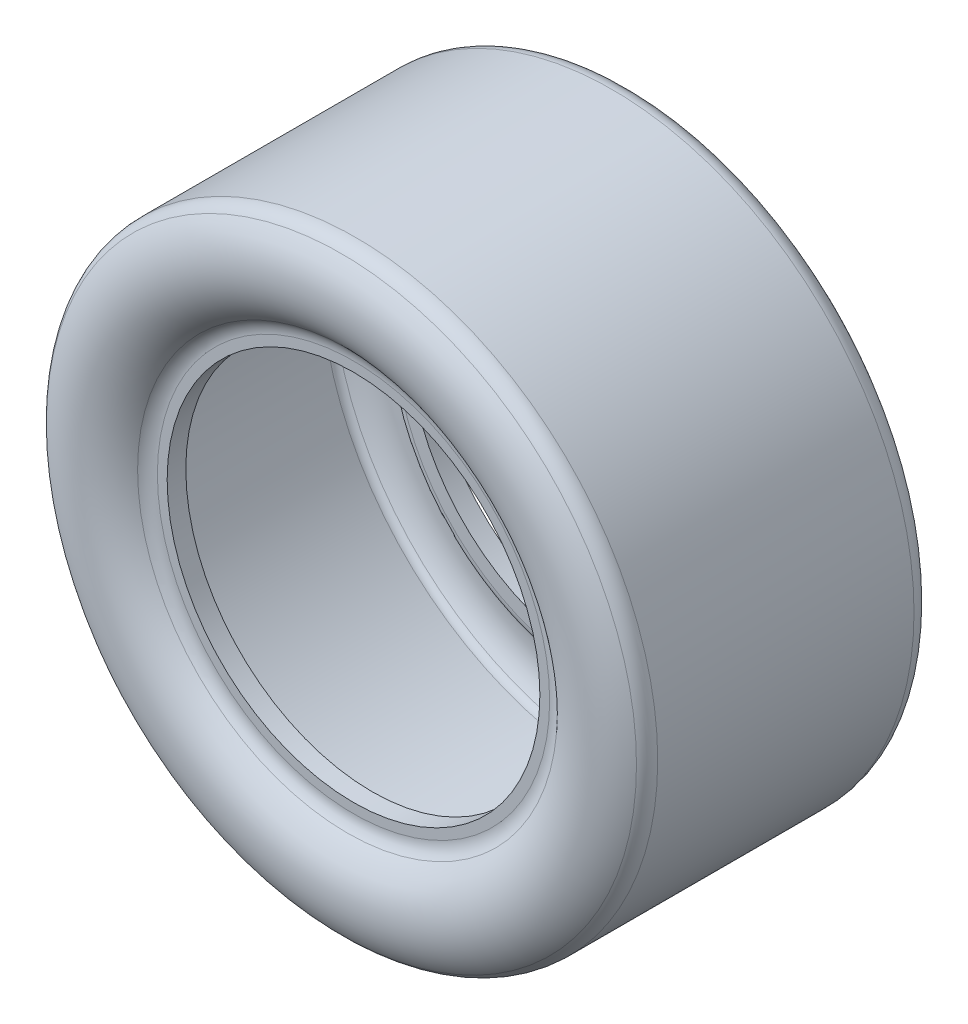
SolidWorks part; units mm, degrees
material "Tire Rubber"
ref_plane "X-Z Datum" through (0, 0, 0) normal (0, 0, 1) x (1, 0, 0)
ref_plane "X-Y Datum" through (0, 0, 0) normal (0, 1, 0) x (1, 0, 0)
ref_plane "Y-Z Plane" through (0, 0, 0) normal (1, 0, 0) x (0, 0, -1)
sketch "Sketch1" plane through (0, 0, 0) normal (1, 0, 0) x (0, 0, -1)
  line L0 (0, 0) -> (-132272.0706, 0) construction
  line L1 (-92.71, 205.74) -> (92.71, 205.74)
  line L2 (0, 0) -> (0, -132272.0706) construction
  line L4 (-88.9, 127) -> (-88.9, 139.7)
  line L5 (88.9, 127) -> (88.9, 139.7)
  line L6 (-88.9, 127) -> (-76.2, 127)
  line L8 (76.2, 127) -> (88.9, 127)
  line L9 (-76.2, 127) -> (-76.2, 136.7746)
  line L10 (76.2, 127) -> (76.2, 136.7746)
  line L11 (-86.5663, 197.8025) -> (86.5663, 197.8025)
  arc A2 (-92.71, 205.74) -> (-88.9, 139.7) centre (-64.4017, 174.2433) ccw
  arc A3 (92.71, 205.74) -> (88.9, 139.7) centre (64.4017, 174.2433) cw
  arc A4 (-91.5819, 195.3468) -> (-80.4384, 143.7974) centre (-64.4017, 174.2433) ccw
  arc A5 (-86.5663, 197.8025) -> (-91.5819, 195.3468) centre (-86.5663, 191.4525) ccw
  arc A6 (-76.2, 136.7746) -> (-80.4384, 143.7974) centre (-84.1375, 136.7746) ccw
  arc A7 (91.5819, 195.3468) -> (80.4384, 143.7974) centre (64.4017, 174.2433) cw
  arc A8 (86.5663, 197.8025) -> (91.5819, 195.3468) centre (86.5663, 191.4525) cw
  arc A9 (80.4384, 143.7974) -> (76.2, 136.7746) centre (84.1375, 136.7746) ccw
  point P7 (-106.68, 171.8041)
  dimension "D4" = 213.36
  dimension "D9" = 7.9375
  dimension "D10" = 6.35
  dimension "D11" = 7.9375
  dimension "D12" = 7.9375
  dimension "D1" = 185.42
  dimension "D2" = 411.48
  dimension "D3" = 12.7
  dimension "D5" = 177.8
  dimension "D6" = 254
  dimension "D7" = 12.7
  dimension "D8" = 7.9375
revolve "Revolve1" add sketch "Sketch1" angle 360 about L0
fillet "Fillet1" radius 12.7 4 edges at (-139.7, 0, -88.9) (-139.7, 0, 88.9) (-205.74, 0, -92.71) (-205.74, 0, 92.71)
ref_axis "Axis1" [suppressed] through (0, 0, 87.3303) along (0, 0, -1)
sketch "Sketch2" plane through (0, 0, 0) normal (0, 0, 1) x (1, 0, 0)
  circle A0 centre (0, 0) radius 205.74
  dimension "D1" = 411.48
extrude "Boss-Extrude1" [suppressed] add sketch "Sketch2" along normal mid plane 185.42
fillet "Fillet2" [suppressed] radius 25.4
sketch "Sketch3" plane through (0, 0, 0) normal (1, 0, 0) x (0, 0, -1)
  line L0 (0, 0) -> (0, 170833.7536) construction
  line L1 (0, 0) -> (-170833.7536, 0) construction
  line L2 (106.68, 205.74) -> (-106.68, 205.74)
  line L3 (-106.68, 205.74) -> (-106.68, 0)
  line L4 (106.68, 205.74) -> (106.68, 0)
  line L5 (106.68, 0) -> (-106.68, 0)
  point P7 (0, 205.74)
  dimension "D1" = 213.36
  dimension "D2" = 411.48
revolve "Revolve2" [suppressed] add sketch "Sketch3" angle 360 about L1
sketch "Sketch4" plane through (0, 0, 0) normal (0, 0, 1) x (1, 0, 0)
  line L0 (0, 0) -> (0, 101.6731)
move or copy body "Body-Move/Copy2" [suppressed] bodies to move or copy 101
move or copy body "Body-Move/Copy1" [suppressed] bodies to move or copy 101
